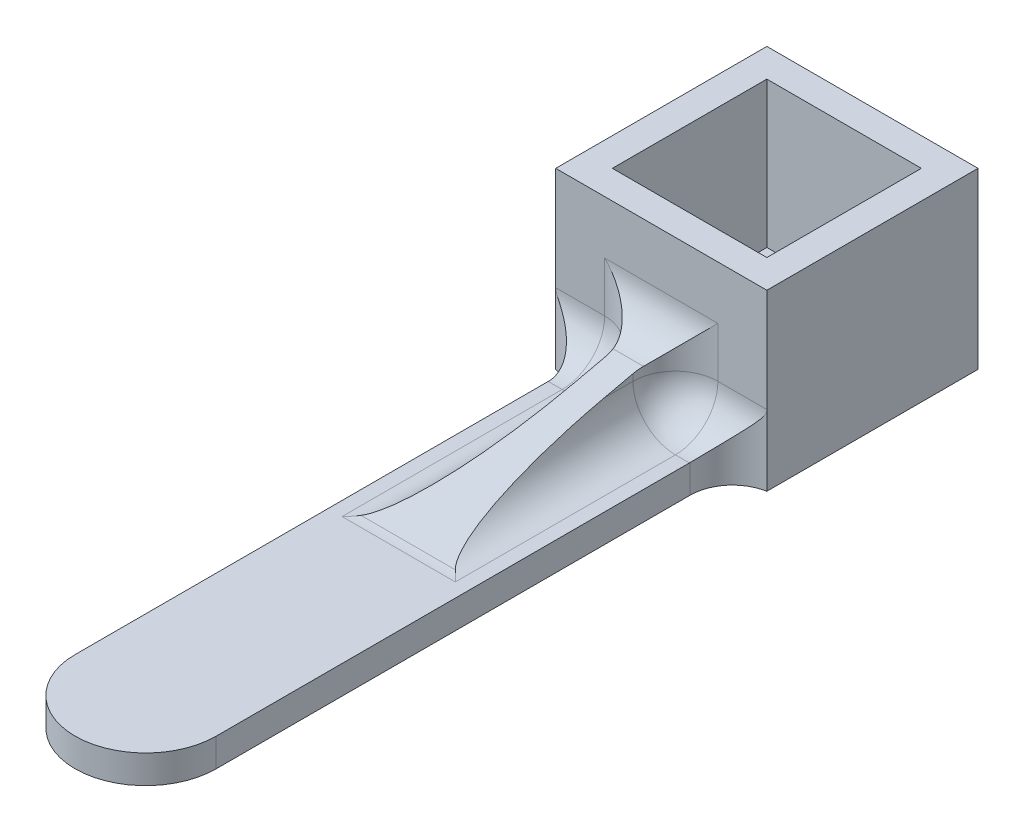
SolidWorks part; units mm, degrees
ref_plane "Front Plane" through (0, 0, 0) normal (0, 0, 1) x (1, 0, 0)
ref_plane "Top Plane" through (0, 0, 0) normal (0, 1, 0) x (1, 0, 0)
ref_plane "Right Plane" through (0, 0, 0) normal (1, 0, 0) x (0, 0, -1)
sketch "Sketch1" plane through (0, 0, 0) normal (0, 1, 0) x (1, 0, 0)
  line L1 (0, 0) -> (10.9139, 0)
  line L2 (0, 0) -> (0, 10.9139)
  line L3 (0, 10.9139) -> (10.9139, 10.9139)
  line L4 (10.9139, 0) -> (10.9139, 10.9139)
  dimension "D1" = 10.9139
extrude "Extrude-Thin1" add sketch "Sketch1" along normal blind 10.3 thin thin type one direction wall 2
sketch "Sketch2" plane through (0, 0, 0) normal (0, -1, 0) x (1, 0, 0)
  line L4 (-2, 2) -> (-2, -12.9139)
  line L5 (-2, -12.9139) -> (12.9139, -12.9139)
  line L6 (12.9139, -12.9139) -> (12.9139, 2)
  line L7 (12.9139, 2) -> (-2, 2)
  line L8 (-2, 2) -> (-2, -12.9139)
  line L9 (-2, -12.9139) -> (12.9139, -12.9139)
  line L10 (12.9139, -12.9139) -> (12.9139, 2)
  line L11 (12.9139, 2) -> (-2, 2)
  dimension "D1" = 0
extrude "Boss-Extrude1" add sketch "Sketch2" along normal blind 2
sketch "Sketch4" plane through (0, -2, 0) normal (0, -1, 0) x (1, 0, 0)
  line L0 (5.457, 2) -> (5.457, 38.4206) construction
  line L1 (12.9139, 2) -> (-2, 2) construction
  line L2 (0.471, 2) -> (0.471, 38.4206)
  line L3 (10.4429, 2) -> (10.4429, 38.4206)
  arc A0 (0.471, 2) -> (10.4429, 2) centre (5.457, 2) ccw
  arc A1 (10.4429, 38.4206) -> (0.471, 38.4206) centre (5.457, 38.4206) ccw
  point P4 (5.457, 20.2103)
  point P9 (6.5, 38.4206)
extrude "Boss-Extrude2" add sketch "Sketch4" against normal blind 2
ref_plane "Plane1" through (5.457, 0, 0) normal (1, 0, 0) x (0, 0, -1)
sketch "Sketch5" plane through (5.457, 0, 0) normal (1, 0, 0) x (0, 0, -1)
  line L0 (-2, 4.15) -> (-20.2103, 0)
  line L1 (-2, 10.3) -> (-2, -2) construction
  line L2 (-2, 0) -> (-38.4206, 0) construction
  line L3 (-2, 4.15) -> (-2, 0)
  line L4 (-2, 0) -> (-20.2103, 0)
extrude "Boss-Extrude3" add sketch "Sketch5" along normal mid plane 2
fillet "Fillet1" radius 3 6 edges at (0.471, -1, 2) (10.4429, -1, 2) (5.457, 4.15, 2) (5.457, 0, 20.2103) (2.464, 0, 2) (8.45, 0, 2)
fillet "Fillet2" radius 3 6 edges at (6.457, 0, 12.7739) (6.457, 0.8787, 2.8787) (4.457, 0, 12.7739) (4.457, 0.8787, 2.8787) (6.457, 4.7716, 2) (4.457, 4.7716, 2)
